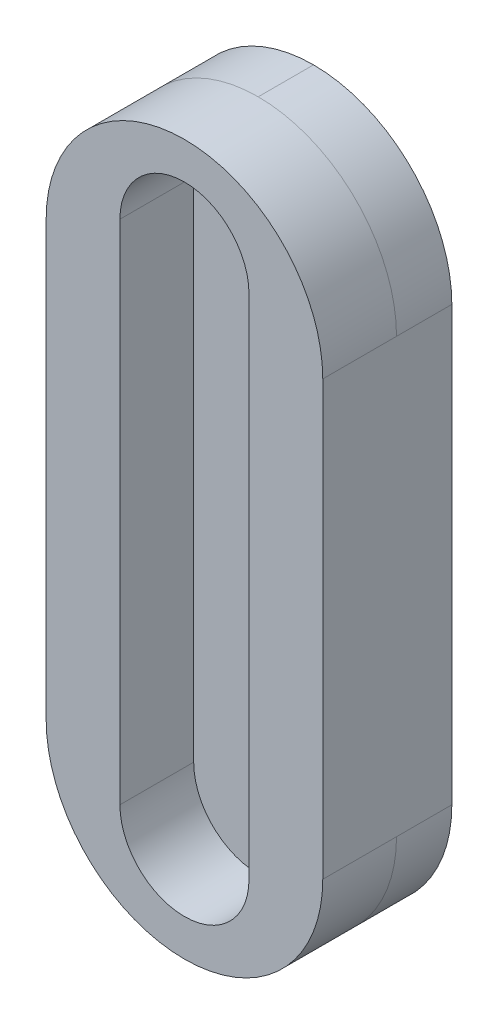
SolidWorks part; units mm, degrees
ref_plane "Front Plane" through (0, 0, 0) normal (0, 0, 1) x (1, 0, 0)
ref_plane "Top Plane" through (0, 0, 0) normal (0, 1, 0) x (1, 0, 0)
ref_plane "Right Plane" through (0, 0, 0) normal (1, 0, 0) x (0, 0, -1)
sketch "Sketch1" plane through (0, 0, 0) normal (0, 0, 1) x (1, 0, 0)
  line L0 (0, 0) -> (0, 24)
  line L1 (-3.75, 8.5) -> (3.75, 8.5)
  line L2 (0, 0) -> (-3.75, 0)
  line L3 (0, 0) -> (0, 27.75)
  line L4 (0, 27.75) -> (-3.75, 27.75)
  line L5 (-3.75, 0) -> (-3.75, 27.75)
  line L6 (0, 0) -> (3.75, 0)
  line L7 (0, 0) -> (0, 27.75)
  line L8 (0, 27.75) -> (3.75, 27.75)
  line L9 (3.75, 0) -> (3.75, 27.75)
  circle A0 centre (0, 24) radius 1.25
  circle A1 centre (0, 20) radius 1.25
  point P25 (0, 0)
extrude "Boss-Extrude1" add sketch "Sketch1" along normal blind 1 contours A1 L0 A0 L7 L4 L5 L1 | A1 L0 L1 L9 L8 L7 A0 region at (-1.9731, 17.8423, 0) region at (1.9731, 17.8423, 0)
sketch "Sketch2" plane through (0, 0, 1) normal (0, 0, 1) x (1, 0, 0)
  line L1 (-3.75, 27.75) -> (3.75, 27.75)
  line L2 (-3.75, 27.75) -> (-3.75, 8.5)
  line L3 (-3.75, 8.5) -> (3.75, 8.5)
  line L4 (3.75, 27.75) -> (3.75, 8.5)
extrude "Boss-Extrude2" add sketch "Sketch2" along normal blind 0.5
sketch "Sketch3" plane through (0, 0, 1.5) normal (0, 0, 1) x (1, 0, 0)
  line L0 (-3.75, 27.75) -> (3.75, 8.5)
  line L1 (0, 12.25) -> (0, 24) construction
  line L2 (-3.75, 12.25) -> (-3.75, 24)
  line L3 (3.75, 12.25) -> (3.75, 24)
  line L4 (3.75, 27.75) -> (-3.75, 27.75) construction
  line L5 (0, 11.25) -> (0, 25) construction
  line L6 (-1.75, 11.25) -> (-1.75, 25)
  line L7 (1.75, 11.25) -> (1.75, 25)
  arc A0 (-3.75, 12.25) -> (3.75, 12.25) centre (0, 12.25) ccw
  arc A1 (3.75, 24) -> (-3.75, 24) centre (0, 24) ccw
  arc A2 (-1.75, 11.25) -> (1.75, 11.25) centre (0, 11.25) ccw
  arc A3 (1.75, 25) -> (-1.75, 25) centre (0, 25) ccw
  point P6 (0, 18.125)
  point P16 (0, 18.125)
  point P21 (0, 26.75)
  line M10 (-3.75, 27.75) -> (-3.75, 8.5)
  line M12 (3.75, 8.5) -> (3.75, 27.75)
  dimension "D3" = 1
  dimension "D1" = 3.5
  dimension "D2" = 2
extrude "Boss-Extrude3" add sketch "Sketch3" along normal blind 2 contours A3 L7 L0 A0 A1 L6 M12 | A2 L6 L0 A1 A0 L7 M10 region at (1.9911, 20.4449, 1.5) region at (-1.9911, 15.8051, 1.5)
fillet "Fillet1" radius 3.75 4 edges at (3.75, 8.5, 0.75) (-3.75, 8.5, 0.75) (3.75, 27.75, 0.75) (-3.75, 27.75, 0.75)
